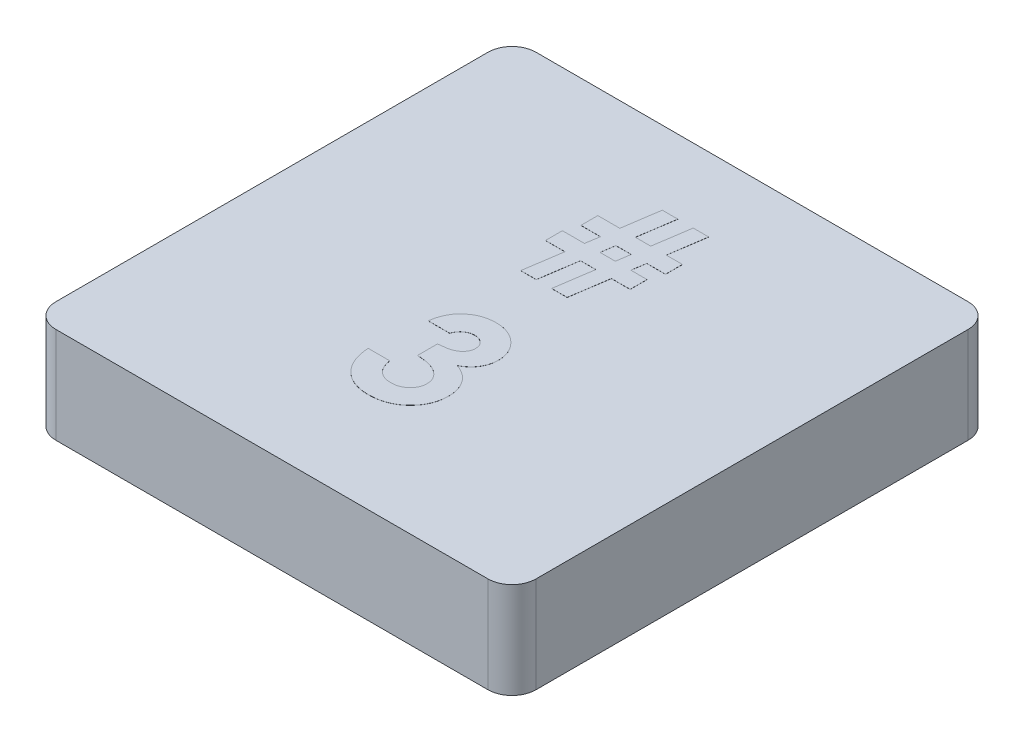
SolidWorks part; units mm, degrees
ref_plane "Front Plane" through (0, 0, 0) normal (0, 0, 1) x (1, 0, 0)
ref_plane "Top Plane" through (0, 0, 0) normal (0, 1, 0) x (1, 0, 0)
ref_plane "Right Plane" through (0, 0, 0) normal (1, 0, 0) x (0, 0, -1)
sketch "Sketch1" plane through (0, 0, 0) normal (0, 1, 0) x (1, 0, 0)
  line L0 (0, 0) -> (12.7, 0)
  line L1 (12.7, 0) -> (12.7, 12.7)
  line L2 (12.7, 12.7) -> (0, 12.7)
  line L3 (0, 12.7) -> (0, 0)
  dimension "D1" = 12.7
  dimension "D2" = 12.7
extrude "Boss-Extrude1" add sketch "Sketch1" along normal blind 2.54
fillet "Fillet1" radius 0.635 4 edges at (0, 1.27, -12.7) (12.7, 1.27, -12.7) (12.7, 1.27, 0) (0, 1.27, 0)
shell "Shell1" thickness 0.635 removed face at (6.35, 0, -6.35)
sketch "Sketch2" plane through (0, 1.905, 0) normal (0, -1, 0) x (-1, 0, 0)
  line L0 (-0.635, 6.35) -> (-12.065, 6.35) construction
  line L1 (-0.635, 12.065) -> (-0.635, 0.635) construction
  line L2 (-12.065, 0.635) -> (-12.065, 12.065) construction
  line L3 (-6.35, 0.635) -> (-6.35, 12.065) construction
  line L4 (-0.635, 0.635) -> (-12.065, 0.635) construction
  line L5 (-12.065, 12.065) -> (-0.635, 12.065) construction
  circle A0 centre (-6.35, 6.35) radius 2.54
  dimension "D1" = 5.08
extrude "Boss-Extrude2" add sketch "Sketch2" along normal up to surface (1.905 mm away) up to face at (6.35, 0, -6.35)
sketch "Sketch4" plane through (0, 2.54, 0) normal (0, 1, 0) x (1, 0, 0)
  line L0 (0, 12.065) -> (0, 0.635) construction
  line L1 (12.065, 12.7) -> (0.635, 12.7) construction
  line L2 (0.635, 0) -> (12.065, 0) construction
  text T0 "<b>3</b>"
  text T1 "<b>#</b>"
  dimension "D1" = 4.953
  dimension "D2" = 5.08
  dimension "D3" = 5.207
  dimension "D4" = 2.7178
extrude "Boss-Extrude4" add sketch "Sketch4" along normal blind 0.0025
